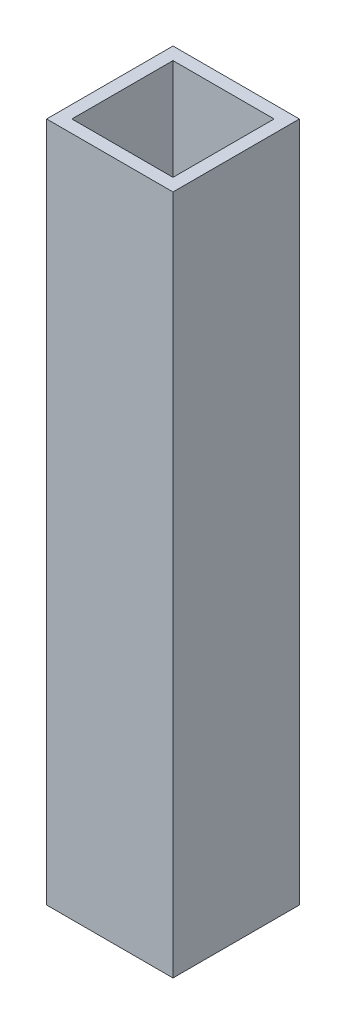
SolidWorks part; units mm, degrees
material "6061 Alloy"
ref_plane "Front Plane" through (0, 0, 0) normal (0, 0, 1) x (1, 0, 0)
ref_plane "Top Plane" through (0, 0, 0) normal (0, 1, 0) x (1, 0, 0)
ref_plane "Right Plane" through (0, 0, 0) normal (1, 0, 0) x (0, 0, -1)
sketch "Sketch1" plane through (0, 0, 0) normal (0, 1, 0) x (1, 0, 0)
  line L1 (0, 0) -> (15, 0)
  line L2 (0, 0) -> (0, 15)
  line L3 (0, 15) -> (15, 15)
  line L4 (15, 0) -> (15, 15)
  dimension "D1" = 15
extrude "Extrude-Thin1" add sketch "Sketch1" along normal blind 80.79 thin thin type one direction reverse wall 1.5
